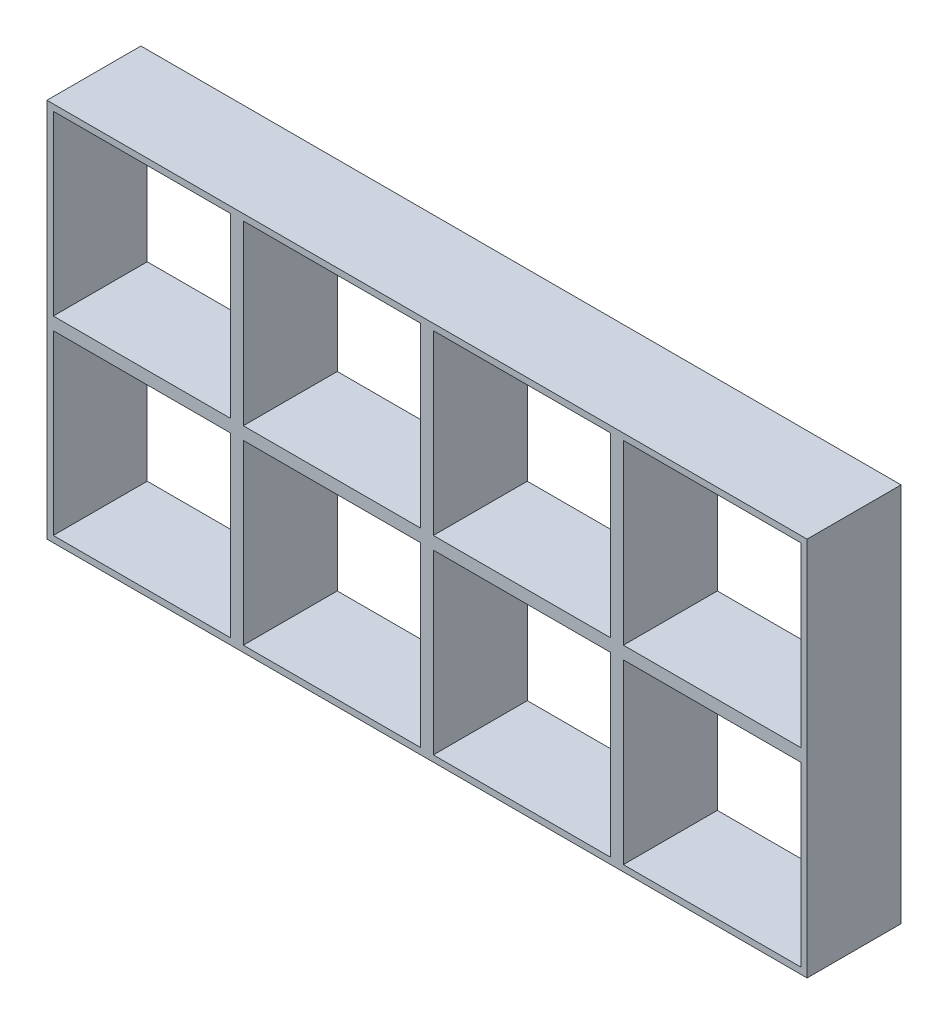
SolidWorks part; units mm, degrees
ref_plane "Plan de face" through (0, 0, 0) normal (0, 0, 1) x (1, 0, 0)
ref_plane "Plan de dessus" through (0, 0, 0) normal (0, 1, 0) x (1, 0, 0)
ref_plane "Plan de droite" through (0, 0, 0) normal (1, 0, 0) x (0, 0, -1)
sketch "Esquisse1" plane through (0, 0, 0) normal (0, 0, 1) x (1, 0, 0)
  line L0 (0, 0) -> (0, 30)
  line L16 (59, 1) -> (59, 29)
  line L17 (59, 29) -> (31, 29)
  line L18 (31, 29) -> (31, 1)
  line L20 (29, 1) -> (29, 29)
  line L21 (29, 29) -> (1, 29)
  line L22 (1, 29) -> (1, 1)
  line L24 (0, 30) -> (120, 30)
  line L25 (60, 30) -> (60, 1) construction
  line L27 (119, 29) -> (119, 1)
  line L28 (91, 29) -> (119, 29)
  line L29 (91, 1) -> (91, 29)
  line L31 (89, 29) -> (89, 1)
  line L32 (61, 29) -> (89, 29)
  line L33 (61, 1) -> (61, 29)
  line L34 (120, 0) -> (120, 30)
  line L35 (0, 0) -> (120, 0)
  line L36 (1, 1) -> (29, 1)
  line L37 (29, 29) -> (31, 29) construction
  line L38 (59, 29) -> (61, 29) construction
  line L39 (89, 29) -> (91, 29) construction
  line L41 (119, 1) -> (120, 1) construction
  line L42 (91, 1) -> (119, 1)
  line L43 (61, 1) -> (89, 1)
  line L44 (31, 1) -> (59, 1)
  dimension "D1" = 1
  dimension "D2" = 1
  dimension "D3" = 2
  dimension "D4" = 30
  dimension "D5" = 1
  dimension "D6" = 28
  dimension "D7" = 28
extrude "Boss.-Extru.1" add sketch "Esquisse1" along normal blind 14.8333 contours L0 L35 L34 L24 L44 L18 L17 L16 L43 L33 L32 L31 L42 L29 L28 L27 L36 L22 L21 L20 region at (60, 15, 0)
mirror "Symétrie1" about plane through (0, 0, 14.8333) normal (0, 1, 0) of "Boss.-Extru.1"
